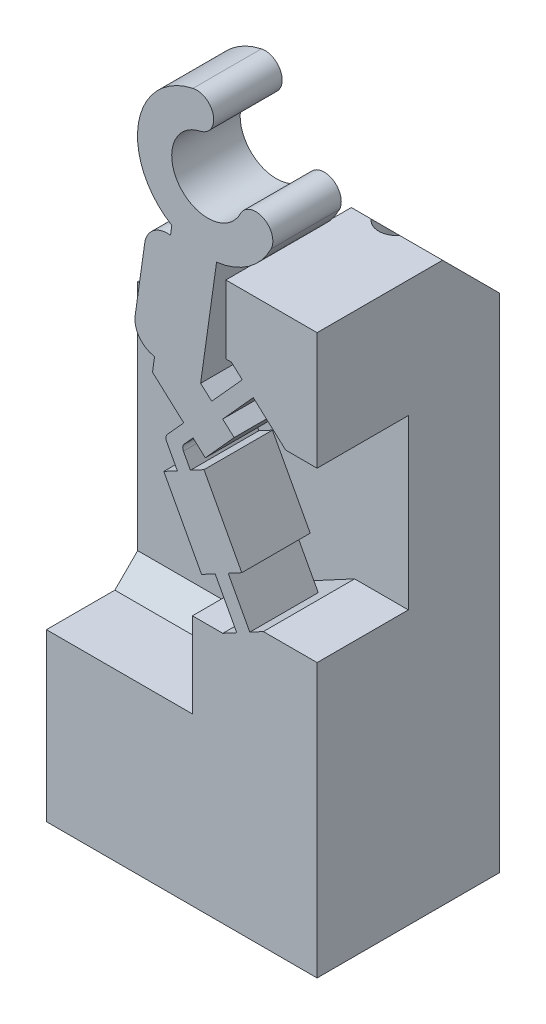
SolidWorks part; units mm, degrees
material "Nylon 6/12"
ref_plane "Front Plane" through (0, 0, 0) normal (0, 0, 1) x (1, 0, 0)
ref_plane "Top Plane" through (0, 0, 0) normal (0, 1, 0) x (1, 0, 0)
ref_plane "Right Plane" through (0, 0, 0) normal (1, 0, 0) x (0, 0, -1)
sketch "Sketch-SkeletonConfigUp" plane through (0, 0, 0) normal (0, 0, 1) x (1, 0, 0)
  line L0 (0, 0) -> (0, -50000) construction
  line L1 (0, 0) -> (4.5811, 6.2164) construction
  line L2 (9.8143, 13.3177) -> (4.5811, 13.945) construction
  line L3 (4.5811, 13.945) -> (1.9779, 11.0613) construction
  line L4 (1.9779, 11.0613) -> (4.5811, 6.2164) construction
  line L5 (4.5811, 13.945) -> (7.7356, 18.3956) construction
  line L6 (1.9779, 11.0613) -> (3.5045, 21.8722) construction
  line L7 (4.5811, 6.2164) -> (9.8143, 13.3177) construction
  line L8 (-587.3593, -797.0242) -> (9.8143, 13.3177) construction
  dimension "D2" = 7.7221
  dimension "D3" = 8.8212
  dimension "D4" = 5.2707
  dimension "D5" = 119.553
  dimension "D6" = 3.8848
  dimension "D7" = 5.4552
  dimension "D8" = 10.9181
  dimension "D9" = 5.5
  dimension "D10" = 6.745
  dimension "D11" = 145.964
  dimension "D12" = 143.612
  dimension "D13" = 8.038
sketch "Sketch-SkeletonConfigDown" plane through (0, 0, 0) normal (0, 0, 1) x (1, 0, 0)
  line L0 (0, 0) -> (0, -50000) construction
  line L1 (0, 0) -> (4.5811, 6.2164) construction
  line L2 (9.8143, 13.3177) -> (4.5811, 13.945) construction
  line L3 (4.5811, 13.945) -> (7.1843, 11.0614) construction
  line L4 (7.1843, 11.0614) -> (4.5811, 6.2164) construction
  line L5 (4.5811, 13.945) -> (0.4753, 17.5368) construction
  line L6 (7.1843, 11.0614) -> (-3.4146, 13.6822) construction
  line L7 (4.5811, 6.2164) -> (9.8143, 13.3177) construction
  line L8 (-589.9357, -800.5203) -> (9.8143, 13.3177) construction
  dimension "D2" = 7.7221
  dimension "D3" = 8.8212
  dimension "D4" = 5.2707
  dimension "D5" = 119.553
  dimension "D6" = 3.8848
  dimension "D7" = 5.4552
  dimension "D8" = 10.9181
  dimension "D9" = 5.5
  dimension "D10" = 6.745
  dimension "D11" = 145.964
  dimension "D1" = 143.612
  dimension "D12" = 76.111
ref_plane "Plane-Cam Base" through (12.592, 0, 0) normal (1, 0, 0) x (0, 0, -1)
ref_plane "Plane-Down-to-Up Derailleur Clearance" through (10.092, 0, 0) normal (1, 0, 0) x (0, 0, -1)
ref_plane "Plane-Cam Cavity Roof" through (8.592, 0, 0) normal (1, 0, 0) x (0, 0, -1)
sketch "Sketch-SwitchBossUp" plane through (0, 0, 0) normal (0, 0, 1) x (1, 0, 0)
  line L8 (1.9218, 19.2213) -> (1.8647, 18.8172)
  line L9 (1.9779, 11.0613) -> (3.5045, 21.8722) construction
  line L11 (2.8258, 4.3534) -> (2.8258, 1.1264)
  line L15 (2.1649, 10.0266) -> (2.7375, 10.3343) construction
  line L16 (1.9779, 11.0613) -> (4.5811, 6.2164) construction
  line L19 (3.6698, 13.4205) -> (4.1522, 12.9849) construction
  line L22 (5.0099, 14.905) -> (5.4924, 14.4695) construction
  line L23 (2.4447, 11.9871) -> (1.9057, 12.4737)
  line L32 (4.8674, 6.3703) -> (4.2948, 6.0626) construction
  line L40 (1.609, 11.0613) -> (2.3469, 11.0613) construction
  line L43 (2.874, 4.5093) -> (0.7934, 4.5093) construction
  line L66 (3.5045, 27.8193) -> (3.5045, 50027.8193) construction
  line L74 (0.3152, 14.9963) -> (0.7347, 17.9668)
  line L75 (2.8258, 1.1264) -> (3.2603, 1.1264)
  line L81 (6.9353, 5.8088) -> (10.4375, 5.8088)
  line L82 (3.6161, 16.9158) -> (3.1843, 13.8587) construction
  line L88 (4.2901, 18.3344) -> (7.0567, 18.3344)
  line L92 (4.1604, 9.1122) -> (2.3986, 8.1656) construction
  line L93 (6.4487, 4.4471) -> (5.6239, 3.9968) construction
  line L95 (3.6161, 16.9158) -> (3.8832, 18.808) construction
  line L96 (10.4375, 5.8088) -> (10.4375, 2.56) construction
  line L97 (3.7497, 17.8619) -> (2.9541, 17.9743) construction
  line L101 (2.4512, 10.1805) -> (1.9779, 11.0613) construction
  line L103 (3.5045, 21.8722) -> (5.6, 20.8363) construction
  line L107 (2.4447, 11.9871) -> (2.8513, 11.6201) construction
  line L109 (3.5045, 21.8722) -> (3.008, 24.1564) construction
  line L113 (2.8258, 4.8534) -> (2.8258, 4.3534)
  line L114 (3.3321, 10.6538) -> (2.7375, 10.3343)
  line L115 (7.0567, 18.3344) -> (13.3688, 18.3344)
  line L116 (13.3688, 18.3344) -> (13.3688, 0.8344)
  line L117 (13.3688, 0.8344) -> (5.2195, 0.8344)
  line L119 (10.4375, 13.1877) -> (10.4375, 5.8088)
  line L121 (5.2195, 0.8344) -> (5.2195, 1.7741) construction
  line L122 (4.7682, 5.1817) -> (4.1572, 4.8534)
  line L123 (5.3407, 5.4894) -> (5.9353, 5.8088)
  line L124 (10.4375, 2.56) -> (9.304, 1.4266) construction
  line L125 (12.0045, 9.5844) -> (13.3688, 9.5844) construction
  line L127 (2.8513, 11.6201) -> (3.3903, 11.1335)
  line L130 (6.9353, 1.4266) -> (9.304, 1.4266) construction
  line L132 (2.8258, 4.3534) -> (3.6239, 3.9968) construction
  line L133 (4.3398, 14.1627) -> (4.8223, 13.7272) construction
  line L134 (3.3903, 11.1335) -> (4.6533, 12.5326)
  line L135 (4.1522, 12.9849) -> (4.6533, 12.5326)
  line L141 (4.2399, 1.6979) -> (3.2603, 1.1264) construction
  line L142 (3.2603, 1.1264) -> (3.2603, 0.8344)
  line L143 (12.0045, 19.1883) -> (12.0045, 16.6962) construction
  line L145 (12.0045, 16.6883) -> (12.0045, -49992.0368) construction
  line L149 (6.4487, 4.8534) -> (6.4487, 4.4471) construction
  line L150 (3.2603, 0.8344) -> (5.2195, 0.8344)
  line L151 (3.6239, 3.9968) -> (5.6239, 3.9968) construction
  line L152 (5.0099, 14.905) -> (3.6698, 13.4205)
  line L153 (5.4924, 14.4695) -> (4.1522, 12.9849)
  line L169 (3.8215, 6.9435) -> (4.7682, 5.1817)
  line L170 (5.3407, 5.4894) -> (4.3941, 7.2512)
  line L177 (4.3941, 7.2512) -> (3.8215, 6.9435) construction
  line L180 (5.9353, 5.8088) -> (6.4487, 4.8534) construction
  line L181 (4.1572, 4.8534) -> (2.8258, 4.8534)
  line L184 (4.1572, 4.8534) -> (6.4487, 4.8534) construction
  line L191 (2.1649, 10.0266) -> (1.5703, 9.7071)
  line L197 (3.5802, 7.2175) -> (3.5802, 7.3858) construction
  line L201 (2.8258, 4.3534) -> (2.8258, 3.9968) construction
  line L202 (2.8258, 3.9968) -> (3.6239, 3.9968) construction
  line L204 (5.2195, 1.4968) -> (3.2603, 1.4968) construction
  line L205 (3.2603, 1.4968) -> (3.2603, 1.1264) construction
  line L206 (5.2195, 1.7741) -> (6.299, 1.4266) construction
  line L207 (12.0045, 16.6962) -> (12.0045, 16.6883) construction
  line L208 (5.9353, 5.8088) -> (6.9353, 5.8088)
  line L209 (12.0045, 19.1883) -> (12.0045, 16.6883) construction
  line L211 (5.2195, 1.7741) -> (4.6239, 3.9968) construction
  line L212 (4.2399, 1.6979) -> (3.6239, 3.9968) construction
  line L213 (5.6239, 3.9968) -> (4.6239, 3.9968) construction
  line L215 (4.5343, 15.3344) -> (4.2901, 15.3344)
  line L217 (3.6698, 13.4205) -> (3.1843, 13.8587)
  line L218 (4.3941, 7.2512) -> (4.9887, 7.5706)
  line L219 (6.9353, 5.8088) -> (6.9353, 1.4266) construction
  line L225 (3.1843, 13.8587) -> (3.8832, 18.808)
  line L226 (4.2901, 15.3344) -> (4.2901, 18.3344)
  line L235 (1.8647, 18.8172) -> (1.0749, 13.2238) construction
  line L236 (1.5703, 9.7071) -> (3.2269, 6.624)
  line L237 (1.0749, 13.2238) -> (1.1656, 13.8663)
  line L241 (1.9779, 11.0613) -> (2.648, 11.8036) construction
  line L242 (6.299, 1.4266) -> (6.9353, 1.4266) construction
  line L243 (2.7375, 10.3343) -> (2.4302, 10.9062)
  line L244 (2.4649, 11.1921) -> (2.8513, 11.6201)
  line L245 (2.1649, 10.0266) -> (1.6923, 10.9062)
  line L246 (1.727, 11.1921) -> (2.4447, 11.9871)
  line L247 (3.3321, 10.6538) -> (4.9887, 7.5706)
  line L248 (4.7682, 5.1817) -> (5.3407, 5.4894) construction
  line L249 (3.8215, 6.9435) -> (3.2269, 6.624)
  line L250 (1.9057, 12.4737) -> (3.1687, 13.8728) construction
  line L251 (4.5811, 13.945) -> (1.9779, 11.0613) construction
  line L252 (2.5372, 13.1732) -> (4.0218, 11.8331) construction
  line L253 (3.1687, 13.8728) -> (3.1843, 13.8587) construction
  line L254 (1.9057, 12.4737) -> (1.0749, 13.2238)
  line L255 (5.0099, 14.905) -> (4.5343, 15.3344)
  line L256 (5.4924, 14.4695) -> (6.9123, 13.1877)
  line L257 (6.9123, 13.1877) -> (10.4375, 13.1877)
  arc A0 (3.8832, 18.808) -> (6.2723, 20.5039) centre (3.5045, 21.8722) ccw
  arc A1 (1.9218, 19.2213) -> (2.8487, 24.8892) centre (3.5045, 21.8722) cw
  arc A2 (2.8487, 24.8892) -> (3.1673, 23.4235) centre (3.008, 24.1564) cw
  arc A3 (6.2723, 20.5039) -> (4.9276, 21.1687) centre (5.6, 20.8363) ccw
  arc A4 (3.1673, 23.4235) -> (4.9276, 21.1687) centre (3.5045, 21.8722) ccw
  arc A19 (0.7347, 17.9668) -> (1.8647, 18.8172) centre (1.7249, 17.827) cw
  circle A28 centre (3.5045, 21.8722) radius 2.3375 construction
  arc A30 (0.3152, 14.9963) -> (1.1656, 13.8663) centre (1.3054, 14.8565) ccw
  arc A31 (2.4302, 10.9062) -> (2.4649, 11.1921) centre (2.6504, 11.0245) cw
  arc A32 (1.6923, 10.9062) -> (1.727, 11.1921) centre (1.9126, 11.0245) cw
  point P6 (3.2795, 8.6389)
  point P45 (3.2795, 12.5032)
  point P66 (4.5811, 6.2164)
  point P165 (4.5811, 13.945)
  dimension "D23" = 1.5875
  dimension "D24" = 0.75
  dimension "D21" = 0.25
  dimension "D17" = 0.5
  dimension "D9" = 17.5
  dimension "D22" = 1
  dimension "D15" = 45
  dimension "D10" = 15
  dimension "D12" = 2.5
  dimension "D19" = 1
  dimension "D8" = 0.65
  dimension "D27" = 0.65
  dimension "D6" = 0.65
  dimension "D25" = 2
  dimension "D26" = 2
  dimension "D5" = 1
  dimension "D16" = 2
  dimension "D28" = 2
  dimension "D18" = 3
  dimension "D20" = 0
  dimension "D29" = 2
  dimension "D30" = 1
  dimension "D31" = 5
  dimension "D32" = 1
extrude "Boss-Switch Body" add sketch "Sketch-SwitchBossUp" along normal blind 3
sketch "Sketch1" plane through (0, 0, 0) normal (0, 0, -1) x (-1, 0, 0)
  line L0 (-8.2901, 5.8088) -> (-5.9353, 5.8088)
  line L1 (-8.2901, 0.8344) -> (0.4122, 0.8344)
  line L2 (-8.2901, 0.8344) -> (-8.2901, 1.4266)
  line L4 (0.4122, 0.8344) -> (0.4122, 1.1264)
  line L5 (-4.2901, 13.1877) -> (-8.2901, 13.1877)
  line L10 (-8.2901, 13.1877) -> (-8.2901, 18.3344)
  line L11 (-4.2399, 1.6979) -> (-5.2399, 1.6979) construction
  line L12 (-8.2901, 18.3344) -> (-4.2901, 18.3344)
  line L13 (-4.2399, 1.6979) -> (-3.2603, 1.1264) construction
  line L14 (-4.2901, 18.3344) -> (-4.2901, 13.1877)
  line L22 (-3.2603, 0.8344) -> (-13.3688, 0.8344) construction
  line L23 (-2.8258, 1.1264) -> (0.4122, 1.1264)
  line L24 (-5.2399, 1.6979) -> (-6.299, 1.4266) construction
  line L26 (-10.4375, 13.1877) -> (-6.9123, 13.1877) construction
  line L27 (-5.9353, 5.8088) -> (-4.1572, 4.8534)
  line L28 (-4.1572, 4.8534) -> (-2.8258, 4.8534)
  line L29 (-2.8258, 4.8534) -> (-2.8258, 1.1264)
  line L30 (-8.2901, 5.8088) -> (-8.2901, 1.4266)
  line L31 (-6.299, 1.4266) -> (-8.2901, 1.4266) construction
  line L32 (-3.2603, 1.1264) -> (-2.8258, 1.1264) construction
  point P21 (-8.2901, 1.3845)
  dimension "D4" = 4
extrude "Boss-Flange Width" add sketch "Sketch1" along normal blind 5
ref_plane "Plane-Sta2Sit Groove" through (3.5045, 0, 0) normal (1, 0, 0) x (0, 0, -1)
ref_plane "Plane-Cam Outer Surface" through (-8.5755, 0, 0) normal (1, 0, 0) x (0, 0, -1)
ref_plane "Plane-FlangeTop" through (-3.5755, 0, 0) normal (1, 0, 0) x (0, 0, -1)
sketch "Sketch2" plane through (-3.5755, 0, 0) normal (1, 0, 0) x (0, 0, -1)
  line L0 (5, 18.3344) -> (-3, 18.3344) construction
  line L1 (5, 13.1877) -> (1, 13.1877)
  line L2 (5, 13.1877) -> (5, 18.3344)
  line L3 (5, 18.3344) -> (1, 18.3344)
  line L4 (1, 13.1877) -> (1, 18.3344)
  line L5 (5, 13.1877) -> (0, 13.1877) construction
  line L10 (-3, 0.8344) -> (-3, 18.3344) construction
  line L11 (5, 1.1264) -> (-3, 1.1264)
  line L12 (5, 1.1264) -> (5, 0.8344)
  line L13 (5, 0.8344) -> (-3, 0.8344)
  line L14 (-3, 1.1264) -> (-3, 0.8344)
  line L15 (0, 11.0613) -> (0, 21.8722) construction
  line L16 (5, 1.1264) -> (0, 1.1264) construction
  line L17 (5, 5.8088) -> (5, 0.8344) construction
  dimension "D1" = 1
extrude "Boss-Flange Height" add sketch "Sketch2" along normal up to surface (8.2034 mm away)
sketch "Sketch17" plane through (0, 1.1264, 0) normal (0, -1, 0) x (1, 0, 0)
  line L0 (8.2901, -5) -> (-3.5755, -5)
  line L1 (8.2901, -5) -> (-3.5755, -5) construction
  line L2 (-3.5755, -5) -> (-3.5755, -1)
  line L3 (-3.5755, -1) -> (8.2901, -1)
  line L4 (8.2901, -1) -> (8.2901, -5)
  line L5 (-3.5755, -1) -> (-3.5755, -5) construction
  line L6 (8.2901, -5) -> (8.2901, 0) construction
  line L7 (4.2901, -1) -> (-3.5755, -1) construction
extrude "Boss-Flange Support" add sketch "Sketch17" against normal up to surface (12.0613 mm away) up to face at (5.1858, 13.1877, -0.5455)
sketch "Sketch27" plane through (0, 0, 0) normal (0, 0, 1) x (1, 0, 0)
  line L0 (4.2901, 15.3344) -> (4.5343, 15.3344)
  line L1 (4.5343, 15.3344) -> (6.9123, 13.1877)
  line L2 (6.9123, 13.1877) -> (4.2901, 13.1877)
  line L3 (4.2901, 13.1877) -> (8.2901, 13.1877) construction
  line L4 (4.2901, 13.1877) -> (4.2901, 18.3344) construction
  line L5 (4.2901, 13.1877) -> (4.2901, 15.3344)
extrude "Cut-Wall Gap" cut sketch "Sketch27" against normal up to surface (1 mm away) up to face at (3.3754, 8.6622, -1)
sketch "Sketch26" plane through (0, 0, -1) normal (0, 0, 1) x (1, 0, 0)
  line L0 (4.2901, 18.3344) -> (-3.5755, 18.3344)
  line L1 (-3.5755, 18.3344) -> (-3.5755, 12.3344)
  line L2 (-3.5755, 18.3344) -> (-3.5755, 1.1264) construction
  line L3 (-3.5755, 12.3344) -> (4.2901, 12.3344)
  line L4 (4.2901, 12.3344) -> (4.2901, 18.3344)
  dimension "D1" = 6
extrude "Cut-Cam Slope Clearance" cut sketch "Sketch26" against normal through all
ref_plane "Plane-Tap Depth" through (0, 7.3344, 0) normal (0, 1, 0) x (1, 0, 0)
sketch "Sketch-HolePositions" plane through (0, 0.8344, 0) normal (0, -1, 0) x (1, 0, 0)
  line L0 (-3.5755, -3) -> (8.2901, -3) construction
  line L1 (8.2901, -5) -> (-3.5755, -5) construction
  line L2 (8.2901, -5) -> (8.2901, 0) construction
  line L4 (-3.5755, -22.2167) -> (-3.5755, 22.2167) construction
  point P6 (-0.5755, -3)
  point P7 (5.7901, -3)
  dimension "D1" = 3
  dimension "D2" = 2.5
  dimension "D3" = 2
sketch "Sketch6" plane through (0, 0.8344, 0) normal (0, -1, 0) x (-1, 0, 0)
  point P0 (0.5755, 3)
  point P3 (-5.7901, 3)
hole_wizard "Tap Drill for M2x0.4 Tap1" positions "Sketch6" profile "Sketch5" hole size "M2x0.4" standard "ANSI Metric" end condition through all
sketch "Sketch5" plane through (-0.5755, 0.8344, -3) normal (1, 0, 0) x (0, 0, -1)
  line L0 (0, 0) -> (0, 24.0719)
  line L1 (0, 24.0719) -> (0.8, 24.0719)
  line L2 (0.8, 24.0719) -> (0.8, 0)
  line L5 (0.8, 0) -> (0, 0)
  line L11 (0, -6.35) -> (0, 107.95) construction
  dimension "Thru Hole Dia." = 1.6
  dimension "Thru Hole Depth" = 24.0719
sketch "Sketch9" plane through (0, 0.8344, 0) normal (0, -1, 0) x (1, 0, 0)
  point P0 (-0.5755, -3)
  point P3 (5.7901, -3)
hole_wizard "M2 Clearance Hole2" positions "Sketch9" profile "Sketch8" hole size "M2" standard "ANSI Metric"
sketch "Sketch8" plane through (-0.5755, 0.8344, -3) normal (1, 0, 0) x (0, 0, -1)
  line L0 (0, 0) -> (0, 7.221)
  line L1 (0, 7.221) -> (1.2, 6.5)
  line L2 (1.2, 6.5) -> (1.2, 0)
  line L5 (1.2, 0) -> (0, 0)
  line L10 (0, 7.221) -> (-1.2, 6.5) construction
  line L11 (0, -6.35) -> (0, 107.95) construction
  dimension "Hole Dia." = 2.4
  dimension "Hole Depth" = 6.5
  dimension "Drill Angle" = 118
sketch "Sketch-Measurements for Derailleur Ramps" [suppressed] plane through (0, 0, 0) normal (0, 0, 1) x (1, 0, 0)
  line L0 (2.8784, 16.9852) -> (4.2265, 19.8331)
  line L1 (3.5524, 18.4092) -> (3.0492, 18.6474)
  line L2 (1.9779, 11.0613) -> (4.4465, 28.5428) construction
  line L3 (3.0492, 18.6474) -> (-4.0642, 13.8428)
  line L4 (7.1843, 11.0614) -> (-9.9544, 15.2993) construction
  line L5 (3.0492, 18.6474) -> (2.1536, 12.3053)
  line L6 (2.1536, 12.3053) -> (-4.0642, 13.8428)
  line L7 (-0.5075, 16.2451) -> (-0.5075, 18.6474)
  line L8 (-0.5075, 18.6474) -> (3.0492, 18.6474)
  line L9 (7.1843, 11.0614) -> (1.9779, 11.0613)
  line L10 (5.8827, 8.6389) -> (3.2795, 8.6389)
  line L12 (7.1843, 11.0614) -> (4.5811, 6.2164) construction
  line L13 (4.5811, 8.6389) -> (4.5811, 8.7912)
  line L14 (4.5811, 6.2164) -> (5.8827, 8.6389)
  line L15 (1.9779, 11.0613) -> (4.5811, 6.2164) construction
  line L16 (3.2795, 8.6389) -> (4.5811, 6.2164)
  line L17 (5.8827, 8.6389) -> (5.8827, 8.7912)
  dimension "D1" = 3.5567
  dimension "D2" = 1.3016
sketch "Sketch12" [suppressed] plane through (0, 23.1883, 0) normal (0, 1, 0) x (1, 0, 0)
  line L0 (10.0045, 0) -> (12.0045, -3)
  line L1 (12.0045, -3) -> (12.0045, 0)
  line L2 (12.0045, 0) -> (10.0045, 0)
extrude "Cut-Up-to-Down Cantilever Slope" [suppressed] cut sketch "Sketch12" against normal up to next
ref_plane "Plane1" [suppressed] through (0, 6.9404, 0) normal (0, 1, 0) x (1, 0, 0)
sketch "Sketch-Derailleur Location" [suppressed] plane through (0, 6.9404, 0) normal (0, 1, 0) x (1, 0, 0)
  line L0 (12.9465, 0) -> (12.9465, -3)
  line L1 (4.2399, -3) -> (3.2603, -3) construction
  line L2 (-119237.4187, 0) -> (9.8143, 0) construction
  point P0 (12.9465, 0)
  point P8 (12.9465, -1.5)
ref_plane "Plane-Cantilever Cut" [suppressed] through (7.0848, 8.5204, -1.9058) normal (-0.6301, -0.7578, 0.1695) x (-0.7765, 0.6151, -0.1368)
sketch "Sketch14" [suppressed] plane through (7.0848, 8.5204, -1.9058) normal (-0.6301, -0.7578, 0.1695) x (-0.7765, 0.6151, -0.1368)
  line L0 (2.3023, -1.6911) -> (-0.3551, -1.6911)
  line L2 (2.3023, -4.3362) -> (2.3023, -1.6911)
  line L3 (-0.3551, -1.6911) -> (-0.3551, -4.4608)
  line L5 (-0.3551, -4.4608) -> (1.0087, -5.0843)
  line L6 (1.0087, -5.0843) -> (2.3023, -4.3362)
extrude "Cut-Down-to-Up Cantilever Slope" [suppressed] cut sketch "Sketch14" against normal up to next
ref_plane "Plane-Symmetry Plane" through (0, 0, 1.5) normal (0, 0, 1) x (1, 0, 0)
sketch "Sketch-Cable Center Point" plane through (0, 0, 1.5) normal (0, 0, 1) x (1, 0, 0)
  line L0 (3.5045, 21.8722) -> (3.3935, 21.0862)
  line L1 (1.9779, 11.0613) -> (3.5045, 21.8722) construction
  point P0 (3.5045, 21.8722)
  dimension "D1" = 0.7937
chamfer "Chamfer-Flange Support" [suppressed] distance 1.5 angle 45
chamfer "Chamfer-Flange Support 3" distance 1 angle 45 1 edges at (-0.3748, 1.1264, -1)
sketch "Sketch25" plane through (0, 0, 3) normal (0, 0, 1) x (1, 0, 0)
  line L0 (13.3688, 18.3344) -> (13.3688, 0.8344)
  line L1 (13.3688, 0.8344) -> (8.2901, 0.8344)
  line L2 (-3.5755, 0.8344) -> (13.3688, 0.8344) construction
  line L3 (8.2901, 0.8344) -> (8.2901, 18.3344)
  line L4 (13.3688, 18.3344) -> (4.2901, 18.3344) construction
  line L5 (8.2901, 18.3344) -> (13.3688, 18.3344)
  line L6 (8.2901, 13.1877) -> (8.2901, 5.8088) construction
extrude "Cut-Base Removal" cut sketch "Sketch25" against normal up to surface (3 mm away) up to face at (3.0806, 13.1556, 0)
chamfer "Chamfer8" distance 2.5 angle 45 1 edges at (6.2901, 18.3344, -5)
sketch "Sketch28" plane through (0, 0.8344, 0) normal (0, -1, 0) x (1, 0, 0)
  line L0 (-3.5755, 3) -> (8.2901, 3)
  line L1 (8.2901, 3) -> (8.2901, 0)
  line L3 (8.2901, 0) -> (8.2901, -5)
  line L4 (8.2901, -5) -> (-3.5755, -5)
  line L5 (-3.5755, -5) -> (-3.5755, 3)
  circle A0 centre (5.7901, -3) radius 1.2 construction
  circle A1 centre (-0.5755, -3) radius 1.2 construction
  circle A2 centre (5.7901, -3) radius 1.2
  circle A3 centre (-0.5755, -3) radius 1.2
  point P18 (0, 0)
  point P19 (0, 0)
  point P20 (0, 0)
  point P21 (8.2354, 0)
extrude "Boss-Rear Fill" add sketch "Sketch28" along normal blind 7
equation "\"axle-diameter\"=2"
equation "\"switch-thickness\"=12"
equation "\"base-width\"=4.0"
equation "\"axle-bushing-radius\"=3"
equation "\"clearance\"= 0.25"
equation "\"arm-width\"=1.5"
equation "\"min-diameter\"=70"
equation "\"alpha\"=143.6120"
equation "\"gamma\"=119.5526"
equation "\"delta\"=145.9637"
equation "\"epsilon\"=6.7452"
equation "\"l_AB\"=8.8212"
equation "\"l_AC\"=4.4914"
equation "\"l_BD\"=5.2707"
equation "\"l_CD\"=3.8848"
equation "\"l_CE\"=10.9181"
equation "\"l_DF\"=5.4552"
equation "\"l_OA\"=7.7221"
equation "\"D2@Sketch-SkeletonConfigUp\" = \"l_OA\""
equation "\"D3@Sketch-SkeletonConfigUp\" = \"l_AB\""
equation "\"D4@Sketch-SkeletonConfigUp\" = \"l_BD\""
equation "\"D5@Sketch-SkeletonConfigUp\" = \"gamma\""
equation "\"D6@Sketch-SkeletonConfigUp\" = \"l_CD\""
equation "\"D7@Sketch-SkeletonConfigUp\" = \"l_DF\""
equation "\"D8@Sketch-SkeletonConfigUp\" = \"l_CE\""
equation "\"D_groove\"=3.175"
equation "\"D7@Sketch-SkeletonConfigDown\" = \"l_DF\""
equation "\"D6@Sketch-SkeletonConfigDown\" = \"l_CD\""
equation "\"D2@Sketch-SkeletonConfigDown\" = \"l_OA\""
equation "\"D3@Sketch-SkeletonConfigDown\" = \"l_AB\""
equation "\"D9@Sketch-SkeletonConfigDown\"=5.5"
equation "\"D8@Sketch-SkeletonConfigDown\" = \"l_CE\""
equation "\"D5@Sketch-SkeletonConfigDown\" = \"gamma\""
equation "\"D4@Sketch-SkeletonConfigDown\" = \"l_BD\""
equation "\"D1@Sketch-SkeletonConfigDown\" = \"alpha\""
equation "\"hinge_length\"=1.5"
equation "\"hinge_depth\"=0.25"
equation "\"D10@Sketch-SkeletonConfigUp\"=\"epsilon\""
equation "\"D11@Sketch-SkeletonConfigUp\"=\"delta\""
equation "\"D12@Sketch-SkeletonConfigUp\"=\"alpha\""
equation "\"D11@Sketch-SkeletonConfigDown\"=\"delta\""
equation "\"D10@Sketch-SkeletonConfigDown\"=\"epsilon\""
equation "\"EE_dx\"=8.9056"
equation "\"EE_dy\"=8.1898"
equation "\"r_groove\"=\"D_groove\"/2"
equation "\"t_wall\"=25.4/16"
equation "\"width_lower\"=\"D_groove\"+\"t_wall\""
equation "\"cable_to_bottom\"=30.6257"
equation "\"switch_EE-up_base_dy\"=24"
equation "\"switch_EE-down_base_dy\"=16"
equation "\"D_axle\"=25.4/8"
equation "\"D_up_to_down\"=16"
equation "\"D_down_to_up\"=25"
equation "\"t_cam_base\"=7.5"
equation "\"D23@Sketch-SwitchBossUp\"=\"D_groove\"/2"
equation "\"D1@Sketch-Cable Center Point\"=\"D_groove\"/4"
